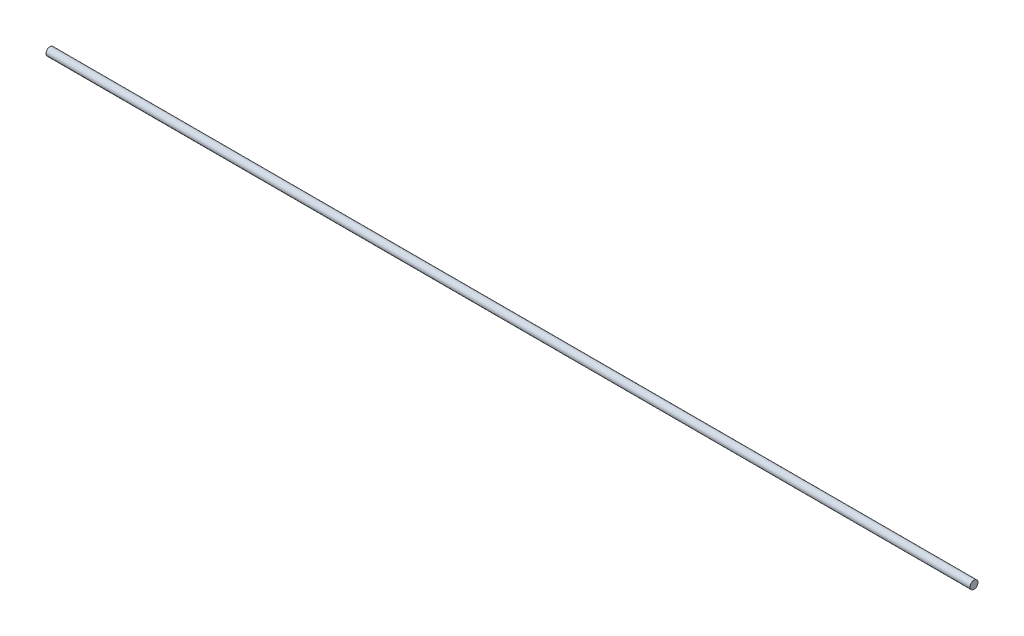
SolidWorks part; units mm, degrees
ref_plane "Front Plane" through (0, 0, 0) normal (0, 0, 1) x (1, 0, 0)
ref_plane "Top Plane" through (0, 0, 0) normal (0, 1, 0) x (1, 0, 0)
ref_plane "Right Plane" through (0, 0, 0) normal (1, 0, 0) x (0, 0, -1)
sketch "Sketch1" plane through (0, 0, 0) normal (1, 0, 0) x (0, 0, -1)
  circle A0 centre (0, 0) radius 3.175
  dimension "D1" = 6.35
extrude "Boss-Extrude1" add sketch "Sketch1" along normal blind 736.6
